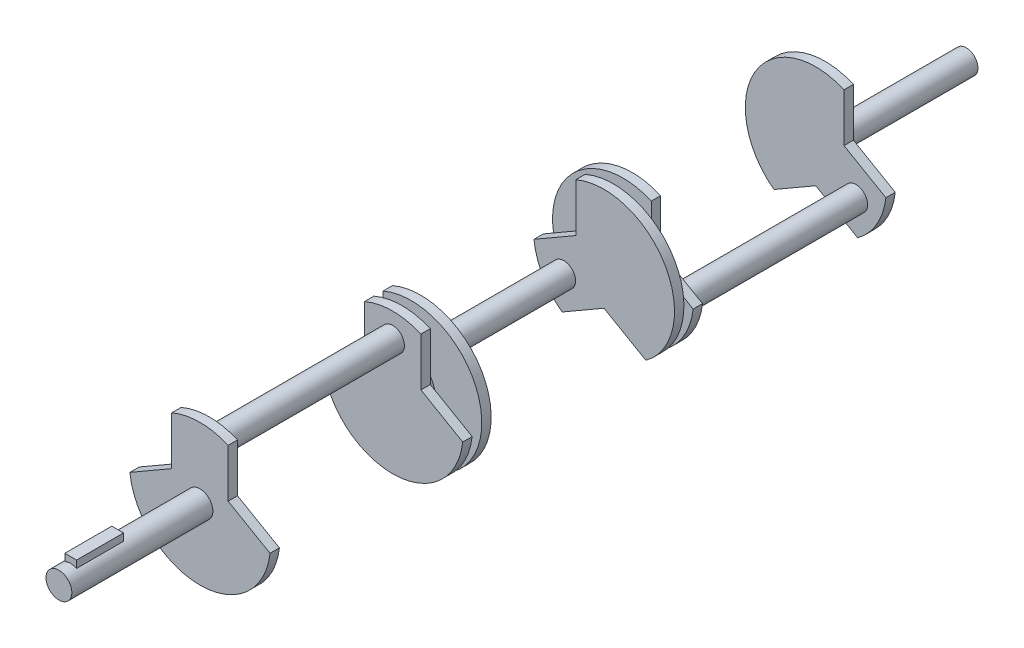
SolidWorks part; units mm, degrees
note: The reader was unsure of these and kept them because the rebuilt part matched: shared geometry of "Sketch5<2>".
ref_plane "Front Plane" through (0, 0, 0) normal (0, 0, 1) x (1, 0, 0)
ref_plane "Top Plane" through (0, 0, 0) normal (0, 1, 0) x (1, 0, 0)
ref_plane "Right Plane" through (0, 0, 0) normal (1, 0, 0) x (0, 0, -1)
sketch "Sketch2" plane through (0, 0, 0) normal (0, 0, 1) x (1, 0, 0)
  line L0 (0, 0) -> (0, 38.1) construction
  line L1 (0, 0) -> (32.9956, -19.05) construction
  line L2 (0, 0) -> (-32.9956, -19.05) construction
  line L3 (15.24, 8.7988) -> (15.24, 34.9192)
  line L4 (-15.24, 8.7988) -> (-15.24, 34.9192)
  line L5 (15.24, 8.7988) -> (37.8609, -4.2614)
  line L6 (-15.24, 8.7988) -> (-37.8609, -4.2614)
  line L7 (-15.24, 0) -> (-15.24, 38.1) construction
  line L8 (-7.62, 13.1982) -> (-40.6156, -5.8518) construction
  line L9 (7.62, 13.1982) -> (40.6156, -5.8518) construction
  line L10 (15.24, 0) -> (15.24, 38.1) construction
  arc A0 (-37.8609, -4.2614) -> (37.8609, -4.2614) centre (0, 0) ccw
  arc A1 (15.24, 34.9192) -> (-15.24, 34.9192) centre (0, 0) ccw
  point P18 (0, 0)
  dimension "D1" = 76.2
  dimension "D2" = 120
  dimension "D3" = 120
  dimension "D4" = 120
  dimension "D5" = 15.24
  dimension "D6" = 15.24
  dimension "D7" = 15.24
  dimension "D8" = 15.24
extrude "Boss-Extrude1" add sketch "Sketch2" against normal blind 5.08
pattern_linear "LPattern1" count 2 spacing 104.14 along (0, 0, 1) of bodies 101
sketch "Sketch3" plane through (0, 0, 0) normal (0, 0, 1) x (1, 0, 0)
  line L0 (0, 25.0388) -> (0, -0.3612) construction
  circle A0 centre (0, 25.0388) radius 6.35
  dimension "D2" = 12.7
  dimension "D1" = 25.4
extrude "Boss-Extrude2" add sketch "Sketch3" along normal up to next
pattern_linear "LPattern2" count 3 spacing 114.3 along (0, 0, 1) of bodies 103
move or copy body "Body-Move/Copy2" bodies to move or copy 104 copy no rotation origin (0, -0.1573, 0) rotation axis (0, 0, 1) rotation angle 120
move or copy body "Body-Move/Copy3" bodies to move or copy 103 copy no rotation origin (0, 0, 0) rotation axis (0, 0, -1) rotation angle 120
sketch "Sketch5" plane through (0, 0, 104.14) normal (0, 0, 1) x (1, 0, 0)
  circle A0 centre (0, 0) radius 12.7
  dimension "D1" = 25.4
extrude "Boss-Extrude3" add sketch "Sketch5" along normal up to next
extrude "Boss-Extrude4" add sketch "Sketch5<2>" along normal up to next from surface
sketch "Sketch5<2>" plane through (0, 0, 104.14) normal (0, 0, 1) x (1, 0, 0) same geometry as "Sketch5"
sketch "Sketch6" plane through (0, 0, 332.74) normal (0, 0, 1) x (1, 0, 0)
  circle A0 centre (0, 0) radius 6.985
  dimension "D1" = 13.97
extrude "Boss-Extrude5" add sketch "Sketch6" along normal blind 76.2
sketch "Sketch7" plane through (0, 0, -5.08) normal (0, 0, -1) x (-1, 0, 0)
  circle A0 centre (0, 0) radius 6.35
  dimension "D1" = 12.7
extrude "Boss-Extrude6" add sketch "Sketch7" along normal blind 76.2
sketch "Sketch8" plane through (0, 0, 0) normal (0, 1, 0) x (1, 0, 0)
  line L0 (0, -332.74) -> (0, -377.19) construction
  line L1 (3.175, -402.59) -> (-3.175, -402.59)
  line L2 (3.175, -402.59) -> (3.175, -377.19)
  line L3 (3.175, -377.19) -> (-3.175, -377.19)
  line L4 (-3.175, -402.59) -> (-3.175, -377.19)
  line L5 (-6.985, -332.74) -> (6.985, -332.74) construction
  dimension "D1" = 25.4
  dimension "D2" = 6.35
  dimension "D3" = 44.45
extrude "Boss-Extrude7" add sketch "Sketch8" against normal up to surface (3.9383 mm away) from offset 10.16
